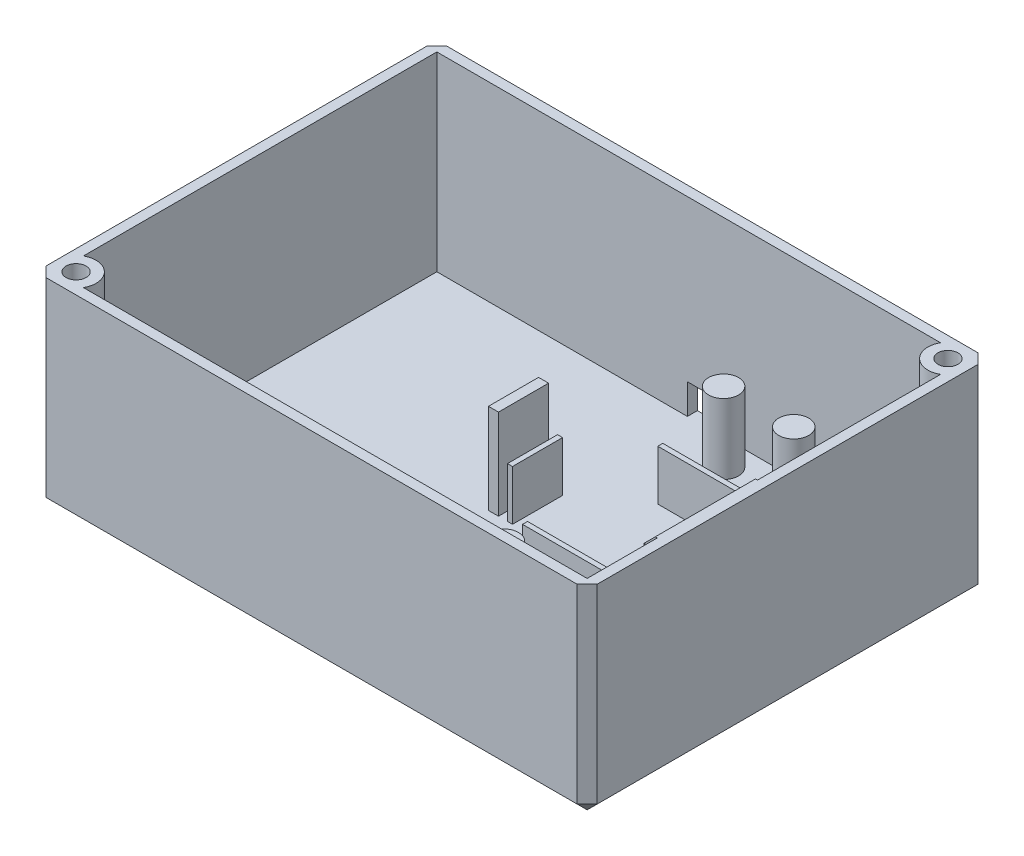
SolidWorks part; units mm, degrees
ref_plane "前视基准面" through (0, 0, 0) normal (0, 0, 1) x (1, 0, 0)
ref_plane "上视基准面" through (0, 0, 0) normal (0, 1, 0) x (1, 0, 0)
ref_plane "右视基准面" through (0, 0, 0) normal (1, 0, 0) x (0, 0, -1)
sketch "草图1" plane through (0, 0, 0) normal (0, 1, 0) x (1, 0, 0)
  line L1 (-27.5, 20) -> (27.5, 20)
  line L2 (-27.5, 20) -> (-27.5, -20)
  line L3 (-27.5, -20) -> (27.5, -20)
  line L4 (27.5, 20) -> (27.5, -20)
  point P4 (0, 20)
  point P7 (27.5, 0)
  dimension "D1" = 55
  dimension "D2" = 40
extrude "凸台-拉伸1" add sketch "草图1" along normal blind 20 contours L1 L4 L3 L2
sketch "草图2" plane through (0, 20, 0) normal (0, 1, 0) x (1, 0, 0)
  line L1 (-27.5, -20) -> (27.5, -20) construction
  line L2 (27.5, 20) -> (27.5, -20) construction
  line L7 (-27.5, 20) -> (27.5, 20) construction
  line L8 (-27.5, 20) -> (-27.5, -20) construction
  circle A0 centre (-25.5, -18) radius 1
  circle A2 centre (25.5, 18) radius 1
  dimension "D1" = 2
  dimension "D4" = 2
  dimension "D2" = 2
  dimension "D3" = 2
  dimension "D5" = 2
  dimension "D6" = 2
extrude "切除-拉伸2" cut sketch "草图2" against normal blind 3 contours A2 | A0 region at (-25.5, 20, 18) region at (25.5, 20, -18)
shell "抽壳1" thickness 1 removed face at (25.5, 20, -17)
chamfer "倒角2" distance 1 angle 45 8 edges at (0, 0, 20) (27.5, 10, 20) (27.5, 0, 0) (27.5, 10, -20) (0, 0, -20) (-27.5, 10, -20) (-27.5, 0, 0) (-27.5, 10, 20)
sketch "草图5" plane through (0, 0, 20) normal (0, 0, 1) x (1, 0, 0)
  line L0 (-26.5, 4) -> (26.5, 4)
  line L1 (-26.5, 20) -> (-26.5, 1) construction
  line L2 (26.5, 1) -> (26.5, 20) construction
  line L3 (-26.5, 1) -> (26.5, 1) construction
  dimension "D1" = 3
sketch "草图6" plane through (-27.5, 0, 0) normal (-1, 0, 0) x (0, 0, 1)
  line L0 (-19, 4) -> (19, 4)
  line L1 (-19, 20) -> (-19, 1) construction
  line L2 (19, 1) -> (19, 20) construction
  line L3 (-19, 1) -> (19, 1) construction
  dimension "D1" = 3
sketch "草图8" plane through (0, 0, -20) normal (0, 0, -1) x (-1, 0, 0)
  line L0 (-26.5, 1) -> (26.5, 1) construction
  line L1 (-1.5, 1) -> (1.5, 1)
  line L2 (-1.5, 1) -> (-1.5, 4)
  line L3 (-1.5, 4) -> (1.5, 4)
  line L4 (1.5, 1) -> (1.5, 4)
  line L5 (26.5, 0) -> (-26.5, 0) construction
  point P6 (0, 1)
  point P9 (0, 0)
  dimension "D1" = 3
  dimension "D2" = 3
extrude "切除-拉伸5" cut sketch "草图8" against normal blind 10
sketch "草图9" plane through (0, 1, 0) normal (0, 1, 0) x (1, 0, 0)
  line L0 (16.55, -14.4) -> (16.55, 14.4)
  line L1 (16.55, -14.4) -> (-16.55, -14.4)
  point P2 (0, -14.4)
  point P4 (16.55, 0)
  dimension "D1" = 28.8
  dimension "D2" = 33.1
sketch "草图10" plane through (0, 20, 0) normal (0, 1, 0) x (1, 0, 0)
  line L0 (26.5, 19) -> (26.5, -19) construction
  line L1 (25, -2) -> (26.5, -2)
  line L2 (25, -2) -> (25, -12)
  line L3 (25, -12) -> (26.5, -12)
  line L5 (26.5, 16.2679) -> (26.5, -19) construction
  line L11 (-23.7679, -19) -> (26.5, -19) construction
  line L12 (26.5, -12) -> (26.5, -2)
  dimension "D1" = 1.5
  dimension "D2" = 10
  dimension "D6" = 7
extrude "凸台-拉伸2" add sketch "草图10" against normal blind 3 contours L3 L12 L1 L2
sketch "草图11" plane through (0, 1, 0) normal (0, 1, 0) x (1, 0, 0)
  line L5 (9.6, -12.1) -> (14.6, -12.1)
  line L6 (9.6, -12.1) -> (9.6, -13.1)
  line L7 (9.6, -13.1) -> (14.6, -13.1)
  line L8 (14.6, -12.1) -> (14.6, -13.1)
  line L9 (-3.3, 0.95) -> (-2.3, 0.95)
  line L10 (-3.3, 0.95) -> (-3.3, 5.95)
  line L11 (-3.3, 5.95) -> (-2.3, 5.95)
  line L12 (-2.3, 0.95) -> (-2.3, 5.95)
  line L18 (25.1, 5.95) -> (25.6, 5.95)
  line L31 (4.6, 9.95) -> (19.6, 9.95)
  line L32 (4.6, 9.95) -> (4.6, 10.45)
  line L33 (4.6, 10.45) -> (19.6, 10.45)
  line L34 (19.6, 9.95) -> (19.6, 10.45)
  line L35 (4.6, -3.05) -> (19.6, -3.05)
  line L36 (4.6, -3.05) -> (4.6, -3.55)
  line L37 (4.6, -3.55) -> (19.6, -3.55)
  line L38 (19.6, -3.05) -> (19.6, -3.55)
  line L43 (-1.4, 5.95) -> (-0.9, 5.95)
  line L44 (-1.4, 5.95) -> (-1.4, 0.95)
  line L45 (-1.4, 0.95) -> (-0.9, 0.95)
  line L46 (-0.9, 5.95) -> (-0.9, 0.95)
  line L47 (25.1, 5.95) -> (25.1, 0.95)
  line L48 (25.1, 0.95) -> (25.6, 0.95)
  line L49 (25.6, 5.95) -> (25.6, 0.95)
  circle A0 centre (4.7, 16.4139) radius 1.5
  circle A1 centre (11.7, 16.4139) radius 1.5
  circle A2 centre (18.7, 16.4139) radius 1.5
  circle A3 centre (7.1, -7.9525) radius 1.5
  circle A4 centre (17.1, -7.9525) radius 1.5
  point P4 (-2.3, 3.45)
  point P15 (12.1, 10.45)
  point P16 (12.1, -3.05)
  point P24 (-1.4, 3.45)
  point P34 (25.1, 3.45)
  point P37 (-0.9, 3.45)
  dimension "D13" = 3
  dimension "D1" = 15
  dimension "D2" = 13
  dimension "D3" = 5
  dimension "D4" = 1
  dimension "D5" = 1
  dimension "D6" = 5
  dimension "D7" = 0.5
  dimension "D8" = 5
  dimension "D9" = 0.5
  dimension "D10" = 5
  dimension "D11" = 0.5
  dimension "D12" = 0.5
  dimension "D14" = 26
  dimension "D15" = 7
  dimension "D16" = 7
extrude "凸台-拉伸6" add sketch "草图11" along normal blind 5 contours L31 L34 L33 L32 | L46 L43 L44 L45 | L38 L35 L36 L37 | L49 L18 L47 L48 region at (25.35, 1, -3.45) region at (12.1, 1, -10.2) region at (12.1, 1, 3.3) region at (-1.15, 1, -3.45)
extrude "凸台-拉伸7" add sketch "草图11<7>" along normal blind 7 contours A0 | A1 | A2 | A4 | A3 region at (4.7, 1, -16.4139) region at (11.7, 1, -16.4139) region at (18.7, 1, -16.4139) region at (7.1, 1, 7.9525) region at (17.1, 1, 7.9525)
sketch "草图11<7>" plane through (0, 1, 0) normal (0, 1, 0) x (1, 0, 0) same geometry as "草图11"
extrude "凸台-拉伸8" add sketch "草图11<8>" along normal blind 9 contours L9 L12 L11 L10 | L8 L5 L6 L7 region at (12.1, 1, 12.6) region at (-2.8, 1, -3.45)
sketch "草图11<8>" plane through (0, 1, 0) normal (0, 1, 0) x (1, 0, 0) same geometry as "草图11"
sketch "草图12" plane through (0, 0, 12) normal (0, 0, 1) x (1, 0, 0)
  line L1 (25, 20) -> (26.5, 20) construction
  line L2 (26.3, 20) -> (25, 18.7)
  line L3 (25, 17) -> (25, 20) construction
  line L7 (26.3, 20) -> (25, 20)
  line L8 (25, 20) -> (25, 18.7)
  dimension "D1" = 45
  dimension "D2" = 1.3
extrude "切除-拉伸6" cut sketch "草图12" against normal blind 10
fillet "圆角1" radius 0.3 4 edges at (25, 17.85, 2) (25, 17.85, 12) (25, 18.7, 7) (25, 17, 7)
